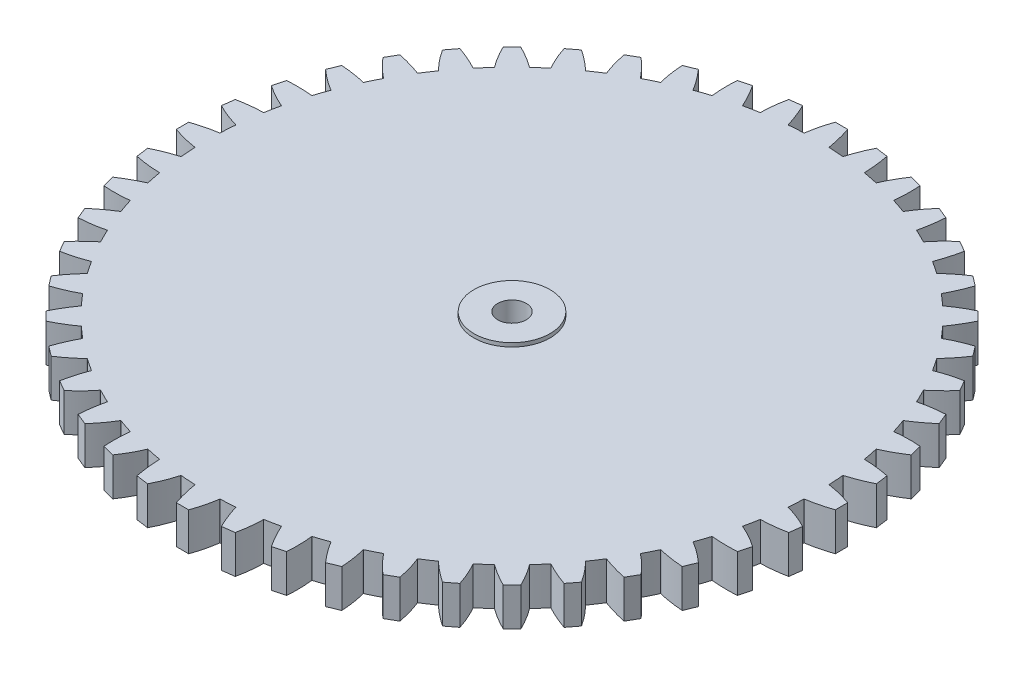
SolidWorks part; units mm, degrees
ref_plane "Front Plane" through (0, 0, 0) normal (0, 0, 1) x (1, 0, 0)
ref_plane "Top Plane" through (0, 0, 0) normal (0, 1, 0) x (1, 0, 0)
ref_plane "Right Plane" through (0, 0, 0) normal (1, 0, 0) x (0, 0, -1)
sketch "Sketch1" plane through (0, 0, 0) normal (0, 1, 0) x (1, 0, 0)
  circle A0 centre (0, 0) radius 16
  dimension "D1" = 32
extrude "Boss-Extrude1" add sketch "Sketch1" along normal blind 2
sketch "Sketch2" plane through (0, 2, 0) normal (0, 1, 0) x (1, 0, 0)
  circle A0 centre (0, 0) radius 0.75
extrude "Cut-Extrude1" cut sketch "Sketch2" against normal blind 2
sketch "Sketch3" plane through (0, 2, 0) normal (0, 1, 0) x (1, 0, 0)
  circle A0 centre (0, 0) radius 2
  circle A1 centre (0, 0) radius 0.75
extrude "Boss-Extrude2" add sketch "Sketch3" along normal blind 0.2 and the other way blind 2.2
sketch "Sketch4" plane through (0, 2, 0) normal (0, 1, 0) x (1, 0, 0)
  line L2 (-0.325, 17.3) -> (0.325, 17.3)
  line L4 (-0.6501, 16) -> (-0.6501, 15.9868)
  line L5 (0.6501, 16) -> (0.6501, 15.9868)
  arc A1 (-0.325, 17.3) -> (-0.6501, 16) centre (6.0564, 15.0137) ccw
  arc A2 (0.325, 17.3) -> (0.6501, 16) centre (-7.3838, 14.6818) cw
  arc A3 (0.6501, 15.9868) -> (-0.6501, 15.9868) centre (0, 0) ccw
  point P10 (0, 17.3)
  point P12 (0, 16)
  dimension "D2" = 0.65
extrude "Boss-Extrude3" add sketch "Sketch4" against normal up to surface (2 mm away) up to face at (0, 0, 2)
ref_axis "Axis1" through (0, 2.32, 0) along (0, -1, 0)
pattern_circular "CirPattern1" count 48 over 360 about axis through (0, 2.32, 0) along (0, -1, 0) of "Boss-Extrude3"
